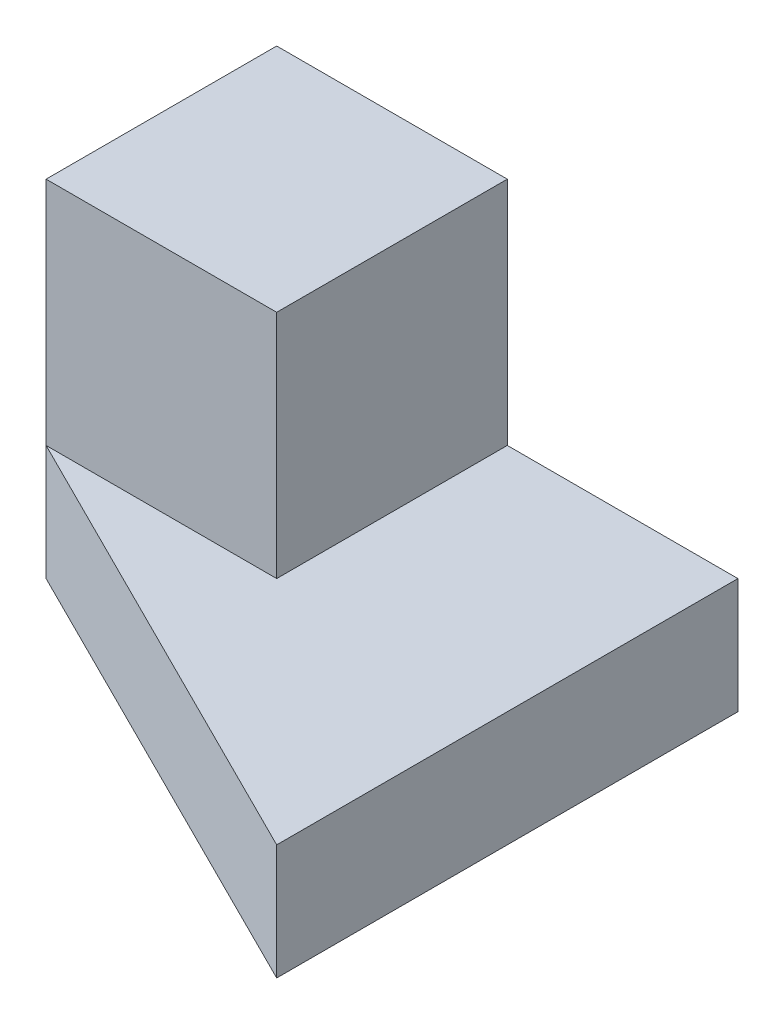
SolidWorks part; units mm, degrees
ref_plane "前基準面" through (0, 0, 0) normal (0, 0, 1) x (1, 0, 0)
ref_plane "上基準面" through (0, 0, 0) normal (0, 1, 0) x (1, 0, 0)
ref_plane "右基準面" through (0, 0, 0) normal (1, 0, 0) x (0, 0, -1)
sketch "草圖1" plane through (0, 0, 0) normal (0, 1, 0) x (1, 0, 0)
  line L0 (0, 0) -> (0, 18.1677) construction
  line L1 (0, 0) -> (0, 10)
  line L2 (0, 10) -> (20, 10)
  line L3 (20, 10) -> (20, -10)
  line L4 (20, -10) -> (0, 0)
  line L5 (10, 10) -> (10, 0)
  line L6 (10, 0) -> (0, 0)
  dimension "D1" = 20
  dimension "D2" = 10
  dimension "D3" = 20
  dimension "D4" = 10
  dimension "D5" = 10
extrude "填料-伸長1" add sketch "草圖1" along normal blind 15 contours L6 L5 L2 L1 region at (5, 0, -5)
extrude "填料-伸長2" add sketch "草圖1<3>" along normal blind 5 contours L5 L6 L4 L3 L2 region at (14.1667, 0, -0.8333)
sketch "草圖1<3>" plane through (0, 0, 0) normal (0, 1, 0) x (1, 0, 0) same geometry as "草圖1"
